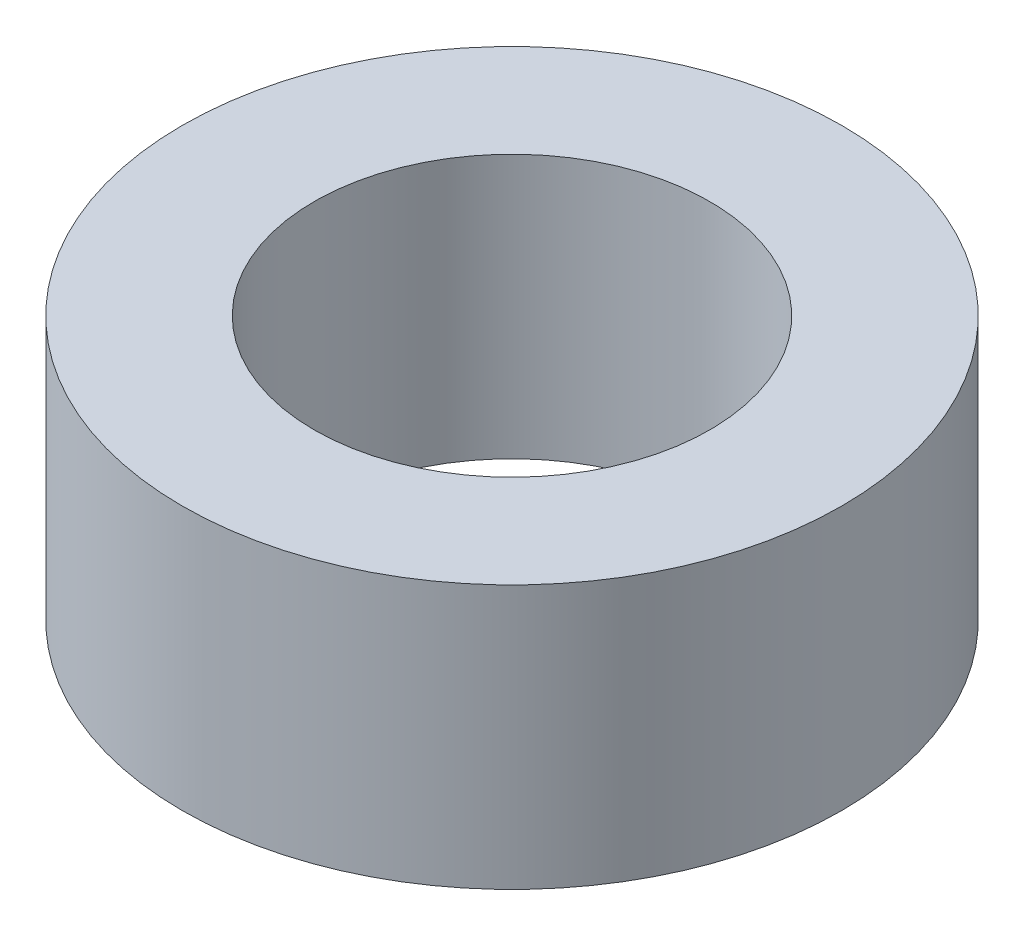
SolidWorks part; units mm, degrees
ref_plane "Front Plane" through (0, 0, 0) normal (0, 0, 1) x (1, 0, 0)
ref_plane "Top Plane" through (0, 0, 0) normal (0, 1, 0) x (1, 0, 0)
ref_plane "Right Plane" through (0, 0, 0) normal (1, 0, 0) x (0, 0, -1)
sketch "Sketch1" plane through (0, 0, 0) normal (0, 1, 0) x (1, 0, 0)
  circle A0 centre (0, 0) radius 3
  circle A1 centre (0, 0) radius 5
  dimension "D1" = 6
  dimension "D2" = 10
extrude "Boss-Extrude1" add sketch "Sketch1" along normal blind 4
